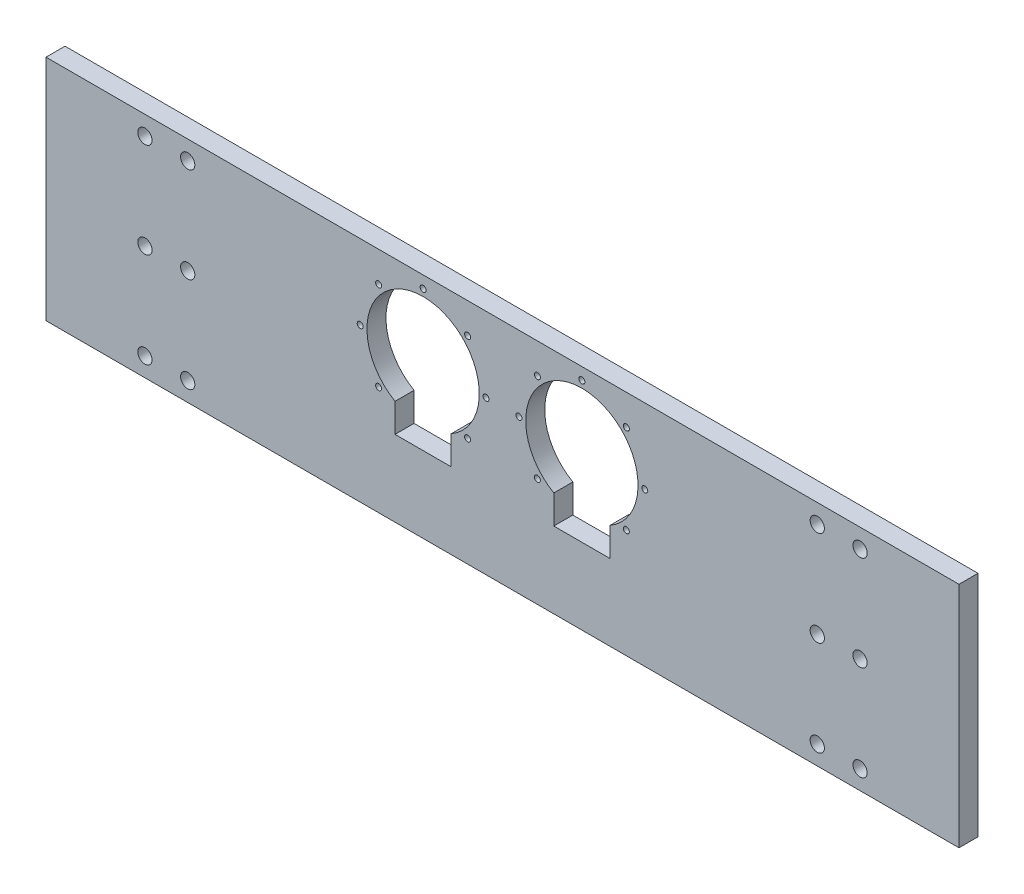
SolidWorks part; units mm, degrees
ref_plane "Front Plane" through (0, 0, 0) normal (0, 0, 1) x (1, 0, 0)
ref_plane "Top Plane" through (0, 0, 0) normal (0, 1, 0) x (1, 0, 0)
ref_plane "Right Plane" through (0, 0, 0) normal (1, 0, 0) x (0, 0, -1)
sketch "Sketch1" plane through (0, 0, 0) normal (0, 0, 1) x (1, 0, 0)
  line L0 (-304.8, 0) -> (304.8, 0) construction
  line L1 (-304.8, 76.2) -> (304.8, 76.2)
  line L2 (-304.8, 76.2) -> (-304.8, -76.2)
  line L3 (-304.8, -76.2) -> (304.8, -76.2)
  line L4 (304.8, 76.2) -> (304.8, -76.2)
  line L5 (-304.8, 76.2) -> (304.8, -76.2) construction
  line L6 (-304.8, -76.2) -> (304.8, 76.2) construction
  line L7 (0, 76.2) -> (0, -76.2) construction
  line L8 (53, 26.2) -> (53, -11.3) construction
  line L9 (53, 26.2) -> (34.25, -6.276) construction
  line L10 (53, 26.2) -> (71.75, -6.276) construction
  line L11 (34.25, -6.276) -> (34.25, -25.4)
  line L12 (71.75, -6.276) -> (71.75, -25.4)
  line L13 (71.75, -25.4) -> (34.25, -25.4)
  line L14 (238.76, 76.2) -> (238.76, -76.2) construction
  line L15 (210.185, 76.2) -> (210.185, -76.2) construction
  line L16 (-34.25, -6.276) -> (-34.25, -25.4)
  line L17 (-71.75, -25.4) -> (-34.25, -25.4)
  line L18 (-71.75, -6.276) -> (-71.75, -25.4)
  circle A5 centre (53, 26.2) radius 48 construction
  arc A6 (71.75, -6.276) -> (34.25, -6.276) centre (53, 26.2) ccw
  circle A7 centre (53, 26.2) radius 42 construction
  circle A8 centre (53, 68.2) radius 2
  circle A9 centre (82.6985, 55.8985) radius 2
  circle A10 centre (95, 26.2) radius 2
  circle A11 centre (82.6985, -3.4985) radius 2
  circle A13 centre (23.3015, -3.4985) radius 2
  circle A14 centre (11, 26.2) radius 2
  circle A15 centre (23.3015, 55.8985) radius 2
  arc A16 (54.9994, -15.7524) -> (51.0006, -15.7524) centre (53, -15.8) ccw [skipped]
  circle A17 centre (238.76, 63.5) radius 4.7625
  circle A18 centre (210.185, 63.5) radius 4.7625
  circle A19 centre (238.76, -63.5) radius 4.7625
  circle A20 centre (210.185, -63.5) radius 4.7625
  circle A21 centre (-82.6985, -3.4985) radius 2
  circle A22 centre (-95, 26.2) radius 2
  circle A23 centre (-82.6985, 55.8985) radius 2
  circle A24 centre (-53, 68.2) radius 2
  circle A25 centre (-23.3015, 55.8985) radius 2
  circle A26 centre (-11, 26.2) radius 2
  circle A27 centre (-23.3015, -3.4985) radius 2
  arc A28 (-71.75, -6.276) -> (-34.25, -6.276) centre (-53, 26.2) cw
  circle A29 centre (-238.76, 63.5) radius 4.7625
  circle A30 centre (-210.185, 63.5) radius 4.7625
  circle A31 centre (-210.185, -63.5) radius 4.7625
  circle A32 centre (-238.76, -63.5) radius 4.7625
  circle A33 centre (210.185, 0) radius 4.7625
  circle A34 centre (238.76, 0) radius 4.7625
  circle A35 centre (-238.76, 0) radius 4.7625
  circle A36 centre (-210.185, 0) radius 4.7625
  point P0 (0, 0)
  point P32 (53, 26.2)
  dimension "D3" = 96
  dimension "D6" = 75
  dimension "D7" = 84
  dimension "D8" = 4
  dimension "D15" = 9.525
  dimension "D17" = 9.525
  dimension "D19" = 9.525
  dimension "D20" = 9.525
  dimension "D1" = 609.6
  dimension "D2" = 152.4
  dimension "D4" = 53
  dimension "D5" = 50
  dimension "D10" = 30
  dimension "D11" = 30
  dimension "D12" = 50.8
  dimension "D13" = 66.04
  dimension "D14" = 28.575
  dimension "D16" = 12.7
  dimension "D18" = 12.7
  dimension "D9" = 8
extrude "Boss-Extrude1" add sketch "Sketch1" along normal blind 12.7
equation "\"bplate_length\"= 24in"
equation "\"bplate_height\"= 6in"
equation "\"bplate_thickness\"= 0.5in"
equation "\"motor_diameter\"= 96 / 25.4in"
equation "\"motor_clearance\"= 5 / 25.4in"
equation "\"motor_mount_hole_pattern_dia\"= 84 / 25.4in"
equation "\"motor_mount_hole_dia\"= 4 / 25.4in"
equation "\"motor_cx\"= \"motor_clearance\" + \"motor_diameter\" / 2in"
equation "\"motor_cy_top\"= \"motor_mount_hole_pattern_dia\" / 2 + \"motor_mount_hole_dia\" * 2in"
equation "\"D1@Sketch1\"=\"bplate_length\""
equation "\"D2@Sketch1\"=\"bplate_height\""
equation "\"motor_driver_cover_dia\"= 75 / 25.4in"
equation "\"D4@Sketch1\"=\"motor_cx\""
equation "\"motor_driver_cutout_clearance\"= 60deg"
equation "\"wire_cutout_clearance\"= 2in"
equation "\"connector_plate_thickness\"= 1in"
equation "\"connector_plate_hole_diameter\"= 0.375in"
equation "\"connector_plate_hole_depth\"= 1in"
equation "\"coonector_first_hole_offset\"= 1.6in"
equation "\"D14@Sketch1\"=\"connector_plate_hole_diameter\"*3in"
equation "\"D13@Sketch1\"=\"coonector_first_hole_offset\"+1in"
equation "\"D12@Sketch1\"=\"wire_cutout_clearance\""
equation "\"D16@Sketch1\"=\"connector_plate_thickness\"/2"
equation "\"D18@Sketch1\"=\"connector_plate_thickness\"/2"
equation "\"D15@Sketch1\"=\"connector_plate_hole_diameter\""
equation "\"D17@Sketch1\"=\"connector_plate_hole_diameter\""
equation "\"D19@Sketch1\"=\"connector_plate_hole_diameter\""
equation "\"D20@Sketch1\"=\"connector_plate_hole_diameter\""
